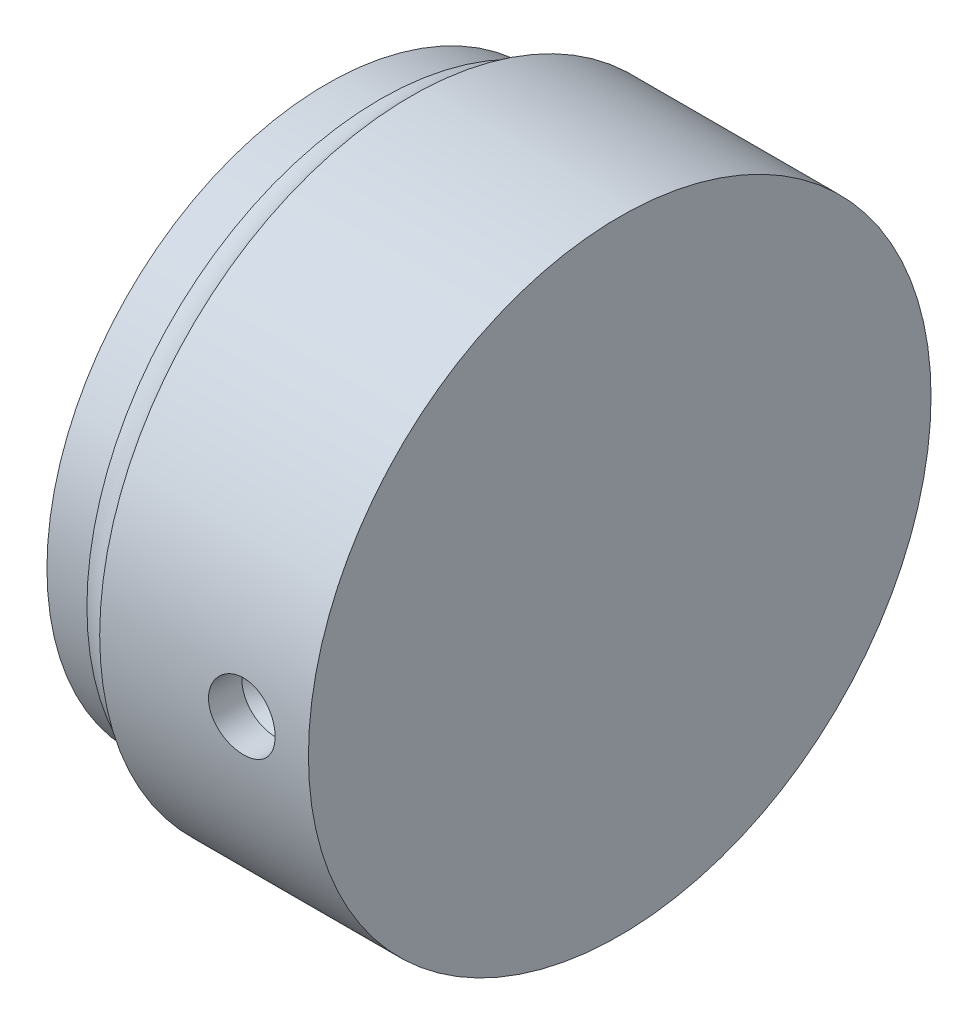
SolidWorks part; units mm, degrees
material "Alloy Steel"
ref_plane "Ön Düzlem" through (0, 0, 0) normal (0, 0, 1) x (1, 0, 0)
ref_plane "Üst Düzlem" through (0, 0, 0) normal (0, 1, 0) x (1, 0, 0)
ref_plane "Sağ Düzlem" through (0, 0, 0) normal (1, 0, 0) x (0, 0, -1)
sketch "Sketch1" plane through (0, 0, 0) normal (0, 0, 1) x (1, 0, 0)
  line L0 (-82.1238, 0) -> (74.4844, 0) construction
  line L1 (-28.8378, -3) -> (-15.7792, -3)
  line L2 (-48.8378, -3) -> (-50.5585, -5.4575)
  line L3 (-50.5585, -5.4575) -> (-50.5585, -22.25)
  line L4 (-50.5585, -22.25) -> (-52.2792, -24.7075)
  line L5 (-52.2792, -24.7075) -> (-52.2792, -30)
  line L6 (-52.2792, -30) -> (-52.2792, -42)
  line L7 (-52.2792, -42) -> (-44.2792, -42)
  line L8 (-44.2792, -42) -> (-44.2792, -44)
  line L9 (-39.6212, -46.7411) -> (-8.2792, -46.7411)
  line L10 (-8.2792, -46.7411) -> (-8.2792, 0)
  line L11 (-8.2792, 0) -> (-15.7792, 0)
  line L12 (-48.8378, -3) -> (-28.8378, -3)
  line L13 (-15.7792, -3) -> (-15.7792, 0)
  arc A0 (-44.2792, -44) -> (-39.6212, -46.7411) centre (-44.2792, -49.3282) cw
  dimension "D1" = 7.5
  dimension "D2" = 22.25
  dimension "D3" = 30
  dimension "D4" = 12
  dimension "D5" = 8
  dimension "D6" = 2
  dimension "D7" = 44
revolve "Revolve1" add sketch "Sketch1" angle 360 about L0
ref_plane "Plane1" through (0, 0, 46.7411) normal (0, 0, 1) x (1, 0, 0)
sketch "Sketch2" plane through (0, 0, 46.7411) normal (0, 0, 1) x (1, 0, 0)
  line L0 (-65.6748, 0) -> (19.6619, 0) construction
  circle A0 centre (-18.2792, 0) radius 2.5
  dimension "D1" = 5
extrude "Cut-Extrude8" cut sketch "Sketch2" against normal up to surface (43.7411 mm away) up to face at (-48.8378, 0, 3)
sketch "Sketch9" plane through (0, 0, 46.7411) normal (0, 0, 1) x (1, 0, 0)
  line L0 (-58.508, 0) -> (7.1321, 0) construction
  circle A0 centre (-18.2792, 0) radius 5
  point P3 (-18.2792, 0)
extrude "Cut-Extrude9" cut sketch "Sketch9" against normal blind 5
chamfer "Chamfer1" distance 2.5 angle 45 1 edges at (-15.7792, 0, 41.7411)
